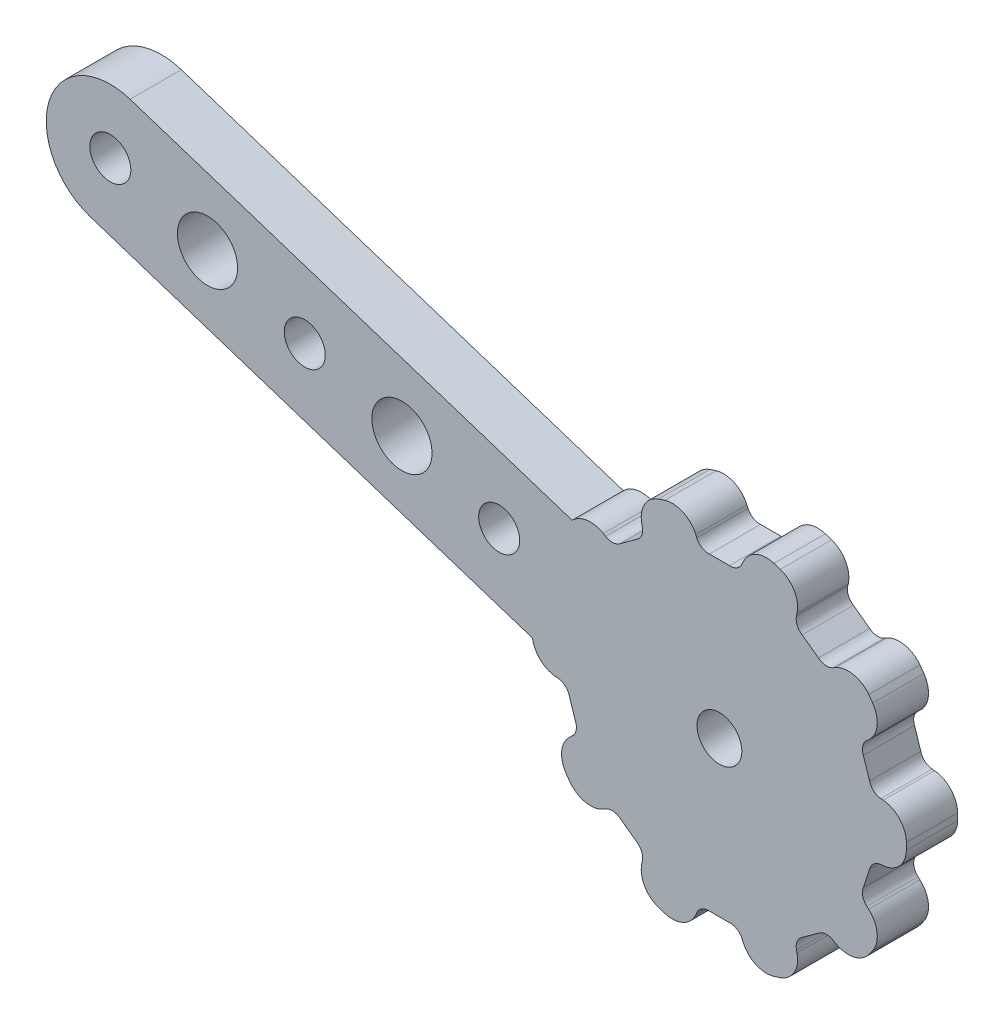
SolidWorks part; units mm, degrees
ref_plane "Front Plane" through (0, 0, 0) normal (0, 0, 1) x (1, 0, 0)
ref_plane "Top Plane" through (0, 0, 0) normal (0, 1, 0) x (1, 0, 0)
ref_plane "Right Plane" through (0, 0, 0) normal (1, 0, 0) x (0, 0, -1)
sketch "Sketch1" plane through (0, 0, 0) normal (0, 0, 1) x (1, 0, 0)
  line L0 (6.4582, 10.2265) -> (7.7303, 9.3022)
  line L1 (-1.5, 0) -> (-1.5, 24.9517) construction
  line L2 (11.2358, 4.4774) -> (11.7217, 2.9819)
  line L3 (0, 0) -> (0, 24.9517) construction
  line L4 (11.7217, -2.9819) -> (11.2358, -4.4774)
  line L5 (0, 0) -> (0, 1.75) construction
  line L6 (1.5, 0) -> (1.5, 0.9014) construction
  line L7 (-1.5, 0) -> (-1.5, 0.9014) construction
  line L8 (1.5, 0) -> (1.5, 24.9517) construction
  line L9 (7.7303, -9.3022) -> (6.4582, -10.2265)
  line L10 (0.7862, -12.0694) -> (-0.7862, -12.0694)
  line L11 (-6.4582, -10.2265) -> (-7.7303, -9.3022)
  line L12 (-11.2358, -4.4774) -> (-11.7217, -2.9819)
  line L13 (-11.7217, 2.9819) -> (-11.2358, 4.4774)
  line L14 (-7.7303, 9.3022) -> (-6.4582, 10.2265)
  line L15 (-0.7862, 12.0694) -> (0.7862, 12.0694)
  circle A0 centre (0, 0) radius 1.75
  circle A4 centre (0, 0) radius 14.5 construction
  arc A5 (12.867, -6.8994) -> (11.509, -5.6025) centre (-1.545, -20.6319) ccw
  arc A6 (10.5378, -10.1052) -> (8.8848, -9.2144) centre (19.1447, 7.8449) cw
  arc A7 (10.5378, -10.1052) -> (12.867, -6.8994) centre (0, 0) ccw
  arc A8 (7.7303, -9.3022) -> (8.8848, -9.2144) centre (8.3694, -10.0713) cw
  arc A9 (11.2358, -4.4774) -> (11.509, -5.6025) centre (12.1647, -4.8476) ccw
  arc A10 (6.3543, -13.1447) -> (6.0179, -11.2974) centre (-13.377, -15.7834) ccw
  arc A11 (2.5856, -14.3692) -> (1.7719, -12.677) centre (20.0995, -4.9063) cw
  arc A12 (2.5856, -14.3692) -> (6.3543, -13.1447) centre (0, 0) ccw
  arc A13 (0.7862, -12.0694) -> (1.7719, -12.677) centre (0.8512, -13.0673) cw
  arc A14 (6.4582, -10.2265) -> (6.0179, -11.2974) centre (6.9921, -11.072) ccw
  arc A15 (14.4649, 1.9813) -> (12.604, 2.2322) centre (10.8772, -17.5996) ccw
  arc A16 (14.4649, -1.9813) -> (12.604, -2.2322) centre (10.8772, 17.5996) cw
  arc A17 (14.4649, -1.9813) -> (14.4649, 1.9813) centre (0, 0) ccw
  arc A18 (11.7217, -2.9819) -> (12.604, -2.2322) centre (12.6908, -3.2285) cw
  arc A19 (11.7217, 2.9819) -> (12.604, 2.2322) centre (12.6908, 3.2285) ccw
  arc A27 (-2.5856, -14.3692) -> (-1.7719, -12.677) centre (-20.0995, -4.9063) ccw
  arc A28 (-6.3543, -13.1447) -> (-6.0179, -11.2974) centre (13.377, -15.7834) cw
  arc A29 (-6.3543, -13.1447) -> (-2.5856, -14.3692) centre (0, 0) ccw
  arc A30 (-6.4582, -10.2265) -> (-6.0179, -11.2974) centre (-6.9921, -11.072) cw
  arc A31 (-0.7862, -12.0694) -> (-1.7719, -12.677) centre (-0.8512, -13.0673) ccw
  arc A32 (-10.5378, -10.1052) -> (-8.8848, -9.2144) centre (-19.1447, 7.8449) ccw
  arc A33 (-12.867, -6.8994) -> (-11.509, -5.6025) centre (1.545, -20.6319) cw
  arc A34 (-12.867, -6.8994) -> (-10.5378, -10.1052) centre (0, 0) ccw
  arc A35 (-11.2358, -4.4774) -> (-11.509, -5.6025) centre (-12.1647, -4.8476) cw
  arc A36 (-7.7303, -9.3022) -> (-8.8848, -9.2144) centre (-8.3694, -10.0713) ccw
  arc A37 (-14.4649, -1.9813) -> (-12.604, -2.2322) centre (-10.8772, 17.5996) ccw
  arc A38 (-14.4649, 1.9813) -> (-12.604, 2.2322) centre (-10.8772, -17.5996) cw
  arc A39 (-14.4649, 1.9813) -> (-14.4649, -1.9813) centre (0, 0) ccw
  arc A40 (-11.7217, 2.9819) -> (-12.604, 2.2322) centre (-12.6908, 3.2285) cw
  arc A41 (-11.7217, -2.9819) -> (-12.604, -2.2322) centre (-12.6908, -3.2285) ccw
  arc A42 (-12.867, 6.8994) -> (-11.509, 5.6025) centre (1.545, 20.6319) ccw
  arc A43 (-10.5378, 10.1052) -> (-8.8848, 9.2144) centre (-19.1447, -7.8449) cw
  arc A44 (-10.5378, 10.1052) -> (-12.867, 6.8994) centre (0, 0) ccw
  arc A45 (-7.7303, 9.3022) -> (-8.8848, 9.2144) centre (-8.3694, 10.0713) cw
  arc A46 (-11.2358, 4.4774) -> (-11.509, 5.6025) centre (-12.1647, 4.8476) ccw
  arc A47 (-6.3543, 13.1447) -> (-6.0179, 11.2974) centre (13.377, 15.7834) ccw
  arc A48 (-2.5856, 14.3692) -> (-1.7719, 12.677) centre (-20.0995, 4.9063) cw
  arc A49 (-2.5856, 14.3692) -> (-6.3543, 13.1447) centre (0, 0) ccw
  arc A50 (-0.7862, 12.0694) -> (-1.7719, 12.677) centre (-0.8512, 13.0673) cw
  arc A51 (-6.4582, 10.2265) -> (-6.0179, 11.2974) centre (-6.9921, 11.072) ccw
  arc A52 (2.5856, 14.3692) -> (1.7719, 12.677) centre (20.0995, 4.9063) ccw
  arc A53 (6.3543, 13.1447) -> (6.0179, 11.2974) centre (-13.377, 15.7834) cw
  arc A54 (6.3543, 13.1447) -> (2.5856, 14.3692) centre (0, 0) ccw
  arc A55 (6.4582, 10.2265) -> (6.0179, 11.2974) centre (6.9921, 11.072) cw
  arc A56 (0.7862, 12.0694) -> (1.7719, 12.677) centre (0.8512, 13.0673) ccw
  arc A57 (10.5378, 10.1052) -> (8.8848, 9.2144) centre (19.1447, -7.8449) ccw
  arc A58 (12.867, 6.8994) -> (11.509, 5.6025) centre (-1.545, 20.6319) cw
  arc A59 (12.867, 6.8994) -> (10.5378, 10.1052) centre (0, 0) ccw
  arc A60 (11.2358, 4.4774) -> (11.509, 5.6025) centre (12.1647, 4.8476) cw
  arc A61 (7.7303, 9.3022) -> (8.8848, 9.2144) centre (8.3694, 10.0713) ccw
  point P44 (-19.23, 0.4774)
  point P131 (0, 0)
  point P151 (0, 0)
  dimension "D1" = 3.5
  dimension "D2" = 10
  dimension "D3" = 14.6
  dimension "D5" = 10
  dimension "D6" = 29
  dimension "D7" = 1
  dimension "D11" = 1.5
  dimension "D12" = 1.5
extrude "Boss-Extrude1" add sketch "Sketch1" along normal blind 4
sketch "Sketch2" plane through (0, 0, 0) normal (0, 0, -1) x (-1, 0, 0)
  line L0 (0, 0) -> (40, 0) construction
  line L5 (7.9655, 7.8455) -> (46.0077, 20.2061)
  line L7 (11.0557, -1.6651) -> (49.0979, 10.6956)
  line L8 (0, 0) -> (47.5528, 15.4508) construction
  line L10 (7.9655, 7.8455) -> (11.0557, -1.6651)
  circle A0 centre (47.5528, 15.4508) radius 1.6
  arc A2 (46.0077, 20.2061) -> (49.0979, 10.6956) centre (47.5528, 15.4508) cw
  circle A3 centre (39.9634, 12.9849) radius 2.35
  circle A4 centre (32.374, 10.5189) radius 1.6
  circle A5 centre (24.7845, 8.053) radius 2.35
  circle A6 centre (17.1951, 5.587) radius 1.6
  point P4 (9.5106, 3.0902)
  dimension "D1" = 3.2
  dimension "D10" = 4.7
  dimension "D11" = 4.7
  dimension "D12" = 3.2
  dimension "D13" = 3.2
  dimension "D2" = 50
  dimension "D3" = 10
  dimension "D4" = 5
  dimension "D5" = 40
  dimension "D6" = 7.98
  dimension "D7" = 7.98
  dimension "D8" = 7.98
  dimension "D9" = 7.98
extrude "Boss-Extrude2" add sketch "Sketch2" along normal blind 4 from surface starting at face at (0, 0, 4)
fillet "Fillet1" radius 2 18 edges at (-10.5378, 10.1052, 2) (-6.3543, 13.1447, 2) (-2.5856, 14.3692, 2) (2.5856, 14.3692, 2) (6.3543, 13.1447, 2) (10.5378, 10.1052, 2) (12.867, 6.8994, 2) (14.4649, 1.9813, 2) (14.4649, -1.9813, 2) (12.867, -6.8994, 2) (10.5378, -10.1052, 2) (6.3543, -13.1447, 2) (2.5856, -14.3692, 2) (-2.5856, -14.3692, 2) (-6.3543, -13.1447, 2) (-10.5378, -10.1052, 2) (-12.867, -6.8994, 2) (-14.4649, -1.9813, 2)
